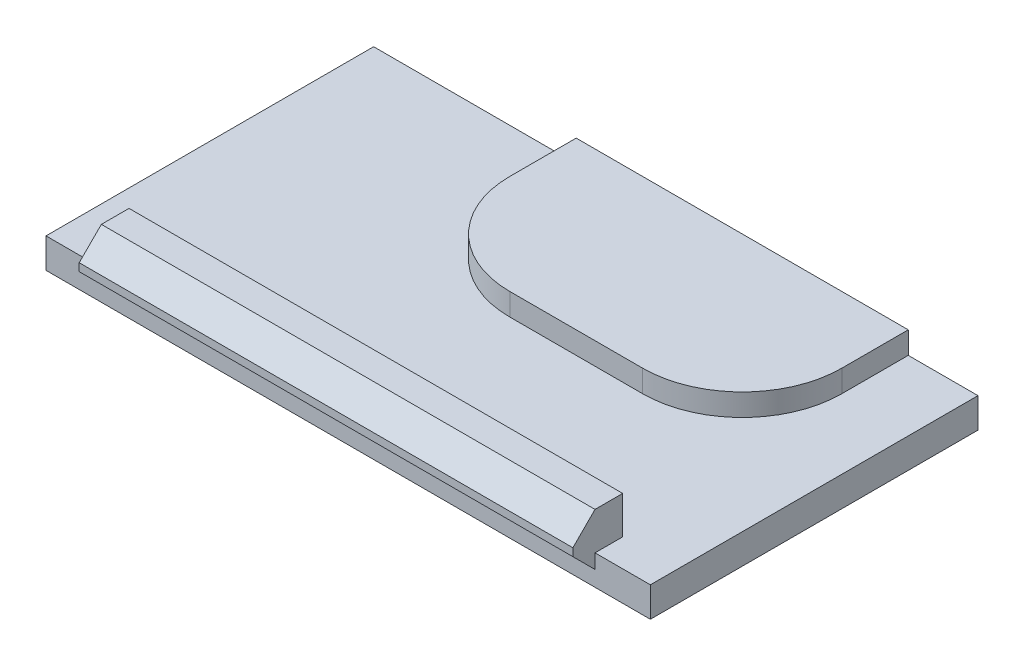
SolidWorks part; units mm, degrees
ref_plane "Front Plane" through (0, 0, 0) normal (0, 0, 1) x (1, 0, 0)
ref_plane "Top Plane" through (0, 0, 0) normal (0, 1, 0) x (1, 0, 0)
ref_plane "Right Plane" through (0, 0, 0) normal (1, 0, 0) x (0, 0, -1)
sketch "Sketch1" plane through (0, 0, 0) normal (0, 1, 0) x (1, 0, 0)
  line L1 (0, 0) -> (69.342, 0)
  line L2 (0, 0) -> (0, 37.592)
  line L3 (0, 37.592) -> (69.342, 37.592)
  line L4 (69.342, 0) -> (69.342, 37.592)
  dimension "D1" = 69.342
  dimension "D2" = 37.592
extrude "Boss-Extrude1" add sketch "Sketch1" along normal blind 3.429
sketch "Sketch3" plane through (0, 0, 0) normal (0, -1, 0) x (1, 0, 0)
  line L0 (34.671, 0) -> (34.671, -22.352) construction
  line L1 (0, 0) -> (69.342, 0) construction
  line L2 (69.342, -37.592) -> (0, -37.592) construction
  line L10 (34.671, -22.352) -> (49.911, -22.352)
  line L11 (57.531, -29.972) -> (57.531, -37.592)
  line L14 (27.051, -29.972) -> (27.051, -37.592)
  line L16 (57.531, -37.592) -> (27.051, -37.592)
  arc A2 (34.671, -22.352) -> (27.051, -29.972) centre (34.671, -29.972) ccw
  arc A3 (57.531, -29.972) -> (49.911, -22.352) centre (49.911, -29.972) ccw
  dimension "D1" = 15.24
  dimension "D3" = 7.62
  dimension "D2" = 15.24
  dimension "D4" = 7.62
  dimension "D5" = 15.24
extrude "Cut-Extrude1" cut sketch "Sketch3" against normal up to surface (3.429 mm away) up to face at (34.671, 3.429, -18.796)
sketch "Sketch5" plane through (0, 0, 0) normal (0, 0, 1) x (1, 0, 0)
  line L0 (0, 3.429) -> (0, 0) construction
  line L1 (6.35, 1.5875) -> (62.992, 1.5875)
  line L2 (6.35, 1.5875) -> (6.35, 7.9375)
  line L3 (6.35, 7.9375) -> (62.992, 7.9375)
  line L4 (62.992, 1.5875) -> (62.992, 7.9375)
  line L5 (69.342, 3.429) -> (69.342, 0) construction
  line L6 (0, 0) -> (69.342, 0) construction
  dimension "D1" = 6.35
  dimension "D2" = 6.35
  dimension "D3" = 1.5875
  dimension "D4" = 6.35
extrude "Boss-Extrude3" add sketch "Sketch5" along normal blind 2.54
chamfer "Chamfer1" distance 2.7305 angle 45 2 edges at (34.671, 1.5875, 2.54) (34.671, 7.9375, 2.54)
sketch "Sketch6" plane through (0, 0, 0) normal (0, 0, -1) x (-1, 0, 0)
  line L5 (-62.992, 7.747) -> (-6.35, 7.747)
  line L6 (-62.992, 7.747) -> (-62.992, 3.429)
  line L7 (-62.992, 3.429) -> (-6.35, 3.429)
  line L8 (-6.35, 7.747) -> (-6.35, 3.429)
extrude "Boss-Extrude4" add sketch "Sketch6" along normal blind 3.175
sketch "Sketch7" plane through (0, 0, 0) normal (0, -1, 0) x (1, 0, 0)
  line L0 (0, -9.017) -> (69.342, -9.017) construction
  line L1 (0, -37.592) -> (0, 0) construction
  line L2 (69.342, 0) -> (69.342, -37.592) construction
  line L4 (49.911, -22.352) -> (34.671, -22.352) construction
  text T0 "<b>BATTERY</b>" font "Arial Rounded MT Bold" height 6.35
  dimension "D1" = 13.335
extrude "Cut-Extrude2" cut sketch "Sketch7" against normal blind 0.4
sketch "Sketch8" plane through (0, 3.429, 0) normal (0, 1, 0) x (1, 0, 0)
  line L0 (61.341, 37.592) -> (61.341, 18.542)
  line L1 (69.342, 37.592) -> (57.531, 37.592) construction
  line L2 (34.671, 18.542) -> (61.341, 18.542)
  line L3 (23.241, 29.972) -> (23.241, 37.592)
  line L4 (27.051, 37.592) -> (0, 37.592) construction
  line L5 (27.051, 29.972) -> (27.051, 37.592) construction
  line L6 (57.531, 37.592) -> (57.531, 29.972) construction
  line L11 (49.911, 22.352) -> (34.671, 22.352) construction
  line L12 (61.341, 37.592) -> (23.241, 37.592)
  arc A0 (23.241, 29.972) -> (34.671, 18.542) centre (34.671, 29.972) ccw
  arc A1 (27.051, 29.972) -> (34.671, 22.352) centre (34.671, 29.972) ccw construction
  arc A2 (49.911, 18.542) -> (61.341, 29.972) centre (49.911, 29.972) ccw
  arc A3 (49.911, 22.352) -> (57.531, 29.972) centre (49.911, 29.972) ccw construction
  line M8 (69.342, 37.592) -> (57.531, 37.592)
  line M9 (57.531, 37.592) -> (57.531, 29.972)
  arc M10 (57.531, 29.972) -> (49.911, 22.352) centre (49.911, 29.972) cw
  line M11 (49.911, 22.352) -> (34.671, 22.352)
  arc M12 (34.671, 22.352) -> (27.051, 29.972) centre (34.671, 29.972) cw
  line M13 (27.051, 29.972) -> (27.051, 37.592)
  line M14 (27.051, 37.592) -> (0, 37.592)
  dimension "D1" = 3.81
  dimension "D2" = 3.81
  dimension "D3" = 3.81
extrude "Boss-Extrude5" add sketch "Sketch8" along normal blind 2.54 contours L2 A2 L0 L3 A0 M8 M9 M10 M11 M12 M13 M14 | L12 M9 M13 M12 M11 M10 region at (60.915, 3.429, -33.782) region at (42.291, 3.429, -30.3075)
sketch "Sketch9" plane through (0, 3.429, 0) normal (0, -1, 0) x (1, 0, 0)
  line L0 (27.051, -37.592) -> (57.531, -37.592)
  line L1 (57.531, -37.592) -> (57.531, -29.972)
  line L2 (49.911, -22.352) -> (34.671, -22.352)
  line L3 (27.051, -37.592) -> (27.051, -29.972)
  arc A0 (27.051, -29.972) -> (34.671, -22.352) centre (34.671, -29.972) cw
  arc A1 (57.531, -29.972) -> (49.911, -22.352) centre (49.911, -29.972) ccw
  arc A2 (34.671, -22.352) -> (27.051, -29.972) centre (34.671, -29.972) ccw construction
  arc A3 (57.531, -29.972) -> (49.911, -22.352) centre (49.911, -29.972) ccw construction
extrude "Cut-Extrude3" cut sketch "Sketch9" against normal blind 0.635
sketch "Sketch10" plane through (0, 0.4, 0) normal (0, -1, 0) x (1, 0, 0)
  line L0 (52.4609, -14.097) -> (53.3241, -14.097) construction
  line L1 (53.3241, -14.097) -> (53.3241, -12.7476) construction
  line L2 (53.3241, -12.7476) -> (52.3332, -12.7476) construction
  line L3 (51.9599, -15.2082) -> (53.9281, -15.2082) construction
  line L4 (54.7529, -14.3798) -> (54.7529, -9.8455) construction
  line L5 (53.9281, -9.017) -> (52.0727, -9.017) construction
  line L6 (52.1769, -11.7157) -> (53.3241, -11.7157) construction
  line L7 (53.3241, -11.7157) -> (53.3241, -10.1282) construction
  line L8 (53.3241, -10.1282) -> (52.1347, -10.1282) construction
  line L9 (43.2807, -10.2436) -> (44.8657, -14.1565) construction
  line L10 (47.1664, -14.097) -> (48.6981, -10.2089) construction
  line L11 (47.3995, -9.7401) -> (47.1329, -10.4457) construction
  line L12 (47.1329, -10.4457) -> (44.8806, -10.4457) construction
  line L13 (44.8806, -10.4457) -> (44.6127, -9.7549) construction
  line L14 (45.2304, -11.557) -> (46.0167, -13.8589) construction
  line L15 (46.0167, -13.8589) -> (46.7819, -11.557) construction
  line L16 (46.7819, -11.557) -> (45.2304, -11.557) construction
  line L17 (38.1809, -15.2082) -> (42.0343, -15.2082) construction
  line L18 (42.0343, -14.0176) -> (40.7829, -14.0176) construction
  line L19 (40.7829, -14.0176) -> (40.7829, -9.7549) construction
  line L20 (39.3541, -9.7549) -> (39.3541, -14.0176) construction
  line L21 (39.3541, -14.0176) -> (38.1809, -14.0176) construction
  line L22 (32.704, -15.2082) -> (36.5574, -15.2082) construction
  line L23 (36.5574, -14.0176) -> (35.306, -14.0176) construction
  line L24 (35.306, -14.0176) -> (35.306, -9.7549) construction
  line L25 (33.8772, -9.7549) -> (33.8772, -14.0176) construction
  line L26 (33.8772, -14.0176) -> (32.704, -14.0176) construction
  line L27 (27.2395, -15.2082) -> (30.4492, -15.2082) construction
  line L28 (31.2579, -14.3798) -> (31.2579, -9.8455) construction
  line L29 (30.4492, -9.017) -> (27.1453, -9.017) construction
  line L30 (27.1453, -10.1282) -> (29.8291, -10.1282) construction
  line L31 (29.8291, -10.1282) -> (29.8291, -11.7157) construction
  line L32 (29.8291, -11.7157) -> (27.4578, -11.7157) construction
  line L33 (27.4578, -12.827) -> (29.8291, -12.827) construction
  line L34 (29.8291, -12.827) -> (29.8291, -14.097) construction
  line L35 (29.8291, -14.097) -> (27.2395, -14.097) construction
  line L36 (16.4147, -9.7562) -> (16.4147, -11.6513) construction
  line L37 (16.4147, -11.6513) -> (14.9339, -13.9097) construction
  line L38 (16.091, -14.541) -> (17.113, -12.7476) construction
  line L39 (17.113, -12.7476) -> (18.1226, -14.541) construction
  line L40 (19.3033, -13.8787) -> (17.8435, -11.6302) construction
  line L41 (17.8435, -11.6302) -> (17.8435, -9.7562) construction
  line L42 (23.0252, -14.097) -> (24.0347, -14.097) construction
  line L43 (24.0347, -14.097) -> (24.0347, -12.5889) construction
  line L44 (24.0347, -12.5889) -> (23.0599, -12.5889) construction
  line L45 (22.3356, -10.5301) -> (21.8532, -9.7339) construction
  line L46 (22.6172, -15.2082) -> (24.6263, -15.2082) construction
  line L47 (25.4635, -14.3823) -> (25.4635, -9.7587) construction
  line L48 (24.0347, -9.7438) -> (24.0347, -11.557) construction
  line L49 (24.0347, -11.557) -> (23.7507, -11.557) construction
  line L50 (52.4609, -14.097) -> (53.3241, -14.097)
  line L51 (53.3241, -14.097) -> (53.3241, -12.7476)
  line L52 (53.3241, -12.7476) -> (52.3332, -12.7476)
  line L53 (51.9599, -15.2082) -> (53.9281, -15.2082)
  line L54 (54.7529, -14.3798) -> (54.7529, -9.8455)
  line L55 (53.9281, -9.017) -> (52.0727, -9.017)
  line L56 (52.1769, -11.7157) -> (53.3241, -11.7157)
  line L57 (53.3241, -11.7157) -> (53.3241, -10.1282)
  line L58 (53.3241, -10.1282) -> (52.1347, -10.1282)
  line L59 (43.2807, -10.2436) -> (44.8657, -14.1565)
  line L60 (47.1664, -14.097) -> (48.6981, -10.2089)
  line L61 (47.3995, -9.7401) -> (47.1329, -10.4457)
  line L62 (47.1329, -10.4457) -> (44.8806, -10.4457)
  line L63 (44.8806, -10.4457) -> (44.6127, -9.7549)
  line L64 (45.2304, -11.557) -> (46.0167, -13.8589)
  line L65 (46.0167, -13.8589) -> (46.7819, -11.557)
  line L66 (46.7819, -11.557) -> (45.2304, -11.557)
  line L67 (38.1809, -15.2082) -> (42.0343, -15.2082)
  line L68 (42.0343, -14.0176) -> (40.7829, -14.0176)
  line L69 (40.7829, -14.0176) -> (40.7829, -9.7549)
  line L70 (39.3541, -9.7549) -> (39.3541, -14.0176)
  line L71 (39.3541, -14.0176) -> (38.1809, -14.0176)
  line L72 (32.704, -15.2082) -> (36.5574, -15.2082)
  line L73 (36.5574, -14.0176) -> (35.306, -14.0176)
  line L74 (35.306, -14.0176) -> (35.306, -9.7549)
  line L75 (33.8772, -9.7549) -> (33.8772, -14.0176)
  line L76 (33.8772, -14.0176) -> (32.704, -14.0176)
  line L77 (27.2395, -15.2082) -> (30.4492, -15.2082)
  line L78 (31.2579, -14.3798) -> (31.2579, -9.8455)
  line L79 (30.4492, -9.017) -> (27.1453, -9.017)
  line L80 (27.1453, -10.1282) -> (29.8291, -10.1282)
  line L81 (29.8291, -10.1282) -> (29.8291, -11.7157)
  line L82 (29.8291, -11.7157) -> (27.4578, -11.7157)
  line L83 (27.4578, -12.827) -> (29.8291, -12.827)
  line L84 (29.8291, -12.827) -> (29.8291, -14.097)
  line L85 (29.8291, -14.097) -> (27.2395, -14.097)
  line L86 (16.4147, -9.7562) -> (16.4147, -11.6513)
  line L87 (16.4147, -11.6513) -> (14.9339, -13.9097)
  line L88 (16.091, -14.541) -> (17.113, -12.7476)
  line L89 (17.113, -12.7476) -> (18.1226, -14.541)
  line L90 (19.3033, -13.8787) -> (17.8435, -11.6302)
  line L91 (17.8435, -11.6302) -> (17.8435, -9.7562)
  line L92 (23.0252, -14.097) -> (24.0347, -14.097)
  line L93 (24.0347, -14.097) -> (24.0347, -12.5889)
  line L94 (24.0347, -12.5889) -> (23.0599, -12.5889)
  line L95 (22.3356, -10.5301) -> (21.8532, -9.7339)
  line L96 (22.6172, -15.2082) -> (24.6263, -15.2082)
  line L97 (25.4635, -14.3823) -> (25.4635, -9.7587)
  line L98 (24.0347, -9.7438) -> (24.0347, -11.557)
  line L99 (24.0347, -11.557) -> (23.7507, -11.557)
  spline S0 degree 3 poles (-1943.9789, -151.7713) (70.8015, -5.7564) (50.7068, -10.4378) (51.201, -13.6216) (51.2243, -13.6995) (51.2587, -13.7692) (51.302, -13.8313) (51.3548, -13.8859) (51.418, -13.9304) (51.4902, -13.9682) (51.5729, -13.9988) (51.6666, -14.0239) (51.7709, -14.0487) (51.8874, -14.064) (52.0145, -14.0802) (52.1532, -14.089) (59.2271, -14.3943) (66.7012, 1.2782) (17.369, -2013.7103) knots -5.753764 -5.753764 -5.753764 -5.753764 0.057159 0.110334 0.159685 0.206314 0.252763 0.298508 0.345397 0.394418 0.448129 0.507403 0.572945 0.645272 0.723434 0.808888 0.901053 13.757311 13.757311 13.757311 13.757311 only from (51.1847, -13.4446) to (52.4609, -14.097) construction
  spline S1 degree 3 poles (27.8312, 1987.0169) (67.0369, -32.6557) (59.2752, -12.2766) (51.9392, -12.7629) (51.7799, -12.7871) (51.6453, -12.8198) (51.5313, -12.8664) (51.4342, -12.9309) (49.1681, -15.1401) (68.6101, -34.1998) (-1532.3859, 1208.2321) knots -18.431036 -18.431036 -18.431036 -18.431036 0.185293 0.345415 0.484392 0.599814 0.701445 0.799771 0.898391 8.784418 8.784418 8.784418 8.784418 only from (52.3332, -12.7476) to (51.2864, -13.111) construction
  spline S2 degree 3 poles (-1741.3145, 873.7381) (75.0574, -19.1103) (52.1018, -10.769) (51.2096, -13.2703) (50.5576, -15.8045) (74.5308, -21.6465) (-1931.6532, 247.6794) knots -21.680999 -21.680999 -21.680999 -21.680999 0.254449 0.501939 0.746908 22.345073 22.345073 22.345073 22.345073 only from (51.2864, -13.111) to (51.1847, -13.4446) construction
  spline S3 degree 3 poles (75.2742, 1990.7471) (73.5276, -23.7791) (62.5688, -8.6736) (51.6082, -9.0272) (51.3953, -9.0456) (51.1961, -9.0671) (51.0106, -9.0958) (50.8392, -9.1364) (46.0755, -10.4981) (48.895, -33.3987) (-622.2815, 1874.0357) knots -20.541444 -20.541444 -20.541444 -20.541444 0.154275 0.299144 0.435657 0.563025 0.682412 0.794474 0.900098 10.150863 10.150863 10.150863 10.150863 only from (52.0727, -9.017) to (50.5311, -9.2415) construction
  spline S4 degree 3 poles (-855.1089, 1773.8437) (67.7349, -22.8697) (54.3326, -7.0026) (50.298, -9.365) (50.1923, -9.437) (50.0934, -9.5151) (50.0036, -9.6016) (49.9178, -9.6914) (49.8432, -9.7905) (49.7502, -9.9266) (49.6557, -10.1086) (49.5748, -10.3396) (48.3854, -15.8394) (80.0906, -24.7646) (-1940.7703, 185.1892) knots -6.819457 -6.819457 -6.819457 -6.819457 0.067226 0.13264 0.196559 0.259324 0.321719 0.383688 0.445686 0.50788 0.631239 0.752454 0.874886 9.044969 9.044969 9.044969 9.044969 only from (50.5311, -9.2415) to (49.5141, -10.829) construction
  spline S5 degree 3 poles (-1948.8407, -90.6734) (67.7035, 0.043) (49.0618, -5.9605) (49.5296, -11.0996) (49.5514, -11.2271) (49.5845, -11.3478) (49.6237, -11.4632) (49.6736, -11.5715) (49.7308, -11.6753) (49.7991, -11.771) (49.8756, -11.8612) (49.9601, -11.9461) (50.0543, -12.0242) (50.1584, -12.0947) (50.27, -12.1608) (50.3908, -12.2201) (55.0009, -14.1417) (66.6884, 3.6787) (-614.5547, -1898.3784) knots -7.400285 -7.400285 -7.400285 -7.400285 0.068275 0.133744 0.197443 0.258623 0.317963 0.376852 0.434131 0.492274 0.549763 0.608348 0.668487 0.729827 0.793456 0.859389 0.927948 8.146244 8.146244 8.146244 8.146244 only from (49.5141, -10.829) to (50.6576, -12.3185) construction
  spline S6 degree 3 poles (-897.2535, 1748.6719) (74.1327, -33.6168) (54.7821, -9.4709) (50.2766, -12.5349) (50.1241, -12.6713) (50.001, -12.8279) (49.904, -13.0009) (49.836, -13.1921) (48.7938, -18.3765) (78.6773, -26.4785) (-1942.2599, 163.412) knots -9.367601 -9.367601 -9.367601 -9.367601 0.137227 0.264577 0.386073 0.503501 0.620912 0.74101 0.866757 10.080854 10.080854 10.080854 10.080854 only from (50.6576, -12.3185) to (49.787, -13.6183) construction
  spline S7 degree 3 poles (-1946.3622, -137.1057) (71.1077, -4.2782) (49.2535, -9.8137) (49.8066, -13.8713) (49.8324, -13.995) (49.8694, -14.1164) (49.9183, -14.2344) (49.9764, -14.3486) (50.0452, -14.4586) (50.1248, -14.5641) (50.2149, -14.6645) (50.3173, -14.7582) (53.9436, -17.663) (70.7025, -1.8777) (-1091.451, -1656.7262) knots -7.489608 -7.489608 -7.489608 -7.489608 0.080578 0.160182 0.239294 0.319412 0.399689 0.480449 0.561571 0.644746 0.729985 0.816279 0.906989 9.502461 9.502461 9.502461 9.502461 only from (49.787, -13.6183) to (50.5522, -14.9267) construction
  spline S8 degree 3 poles (-857.5216, -1796.8604) (53.9426, 10.6843) (46.7348, -13.3983) (50.8327, -15.0633) (50.9896, -15.1136) (51.1592, -15.1504) (51.3414, -15.1749) (51.5357, -15.1955) (59.704, -15.6145) (68.1738, 3.1103) (37.5551, -2015.083) knots -8.780462 -8.780462 -8.780462 -8.780462 0.105008 0.213242 0.326042 0.444876 0.570736 0.705393 0.848096 17.443439 17.443439 17.443439 17.443439 only from (50.5522, -14.9267) to (51.9599, -15.2082) construction
  spline S9 degree 3 poles (155.5885, -2012.5118) (45.847, 4.303) (50.5415, -15.6005) (54.1253, -15.1968) (54.2148, -15.183) (54.2963, -15.1602) (54.3715, -15.1329) (54.4404, -15.1004) (54.5, -15.0581) (54.5546, -15.0121) (54.6021, -14.9585) (54.6417, -14.8964) (54.6763, -14.8283) (54.7057, -14.753) (54.7253, -14.6697) (54.7426, -14.5797) (55.1003, -9.9382) (39.728, -5.0777) (2054.5605, -32.425) knots -7.783832 -7.783832 -7.783832 -7.783832 0.076201 0.148167 0.214256 0.277045 0.3357 0.391934 0.445397 0.497463 0.550131 0.603846 0.660491 0.719468 0.78291 0.850062 0.922854 11.100782 11.100782 11.100782 11.100782 only from (53.9281, -15.2082) to (54.7529, -14.3798) construction
  spline S10 degree 3 poles (2048.4091, 148.4974) (26.3681, -21.4738) (55.6697, -14.1967) (54.7114, -9.4815) (54.6507, -9.3355) (54.5787, -9.2342) (54.5077, -9.1704) (54.4474, -9.1289) (54.3791, -9.0948) (54.3036, -9.0657) (54.2204, -9.044) (54.1296, -9.0276) (49.5866, -8.6633) (44.5929, -24.571) (99.7067, 1990.3965) knots -10.227206 -10.227206 -10.227206 -10.227206 0.147169 0.275723 0.390478 0.496241 0.548237 0.60171 0.658367 0.717356 0.781044 0.849113 0.92192 10.888797 10.888797 10.888797 10.888797 only from (54.7529, -9.8455) to (53.9281, -9.017) construction
  spline S11 degree 3 poles (13.7612, 1989.4029) (64.6234, -25.7659) (58.0308, -9.7722) (51.8582, -10.139) (51.7322, -10.1548) (51.6157, -10.1779) (51.5078, -10.2039) (51.4095, -10.2388) (51.3207, -10.28) (51.2403, -10.3265) (51.171, -10.3821) (51.1092, -10.4413) (51.0577, -10.5084) (51.0156, -10.5814) (50.9829, -10.6611) (50.9595, -10.7464) (50.4611, -14.081) (70.7012, -18.8697) (-1944.5328, 121.9921) knots -11.105427 -11.105427 -11.105427 -11.105427 0.088131 0.171088 0.249183 0.321128 0.389284 0.452942 0.512406 0.568937 0.623027 0.675123 0.726015 0.777734 0.829497 0.883853 0.939923 7.006783 7.006783 7.006783 7.006783 only from (52.1347, -10.1282) to (50.9429, -10.9344) construction
  spline S12 degree 3 poles (-1943.819, -155.0347) (70.5687, -2.8555) (50.4617, -7.7698) (50.9595, -11.1232) (50.9823, -11.209) (51.0173, -11.2871) (51.0583, -11.3596) (51.112, -11.4233) (51.1733, -11.4811) (51.2444, -11.5323) (51.3264, -11.5751) (51.4172, -11.6145) (51.5196, -11.6442) (51.6313, -11.6703) (51.753, -11.6914) (51.8852, -11.706) (57.7181, -12.0627) (64.0114, 6.0503) (14.6689, -2011.2893) knots -5.940677 -5.940677 -5.940677 -5.940677 0.059054 0.114906 0.168336 0.218822 0.269014 0.318338 0.368513 0.420932 0.476046 0.535256 0.599256 0.668251 0.742506 0.822147 0.908161 11.290304 11.290304 11.290304 11.290304 only from (50.9429, -10.9344) to (52.1769, -11.7157) construction
  spline S13 degree 3 poles (1889.0208, 763.3381) (40.1427, -30.9104) (48.1046, -17.6856) (44.4871, -9.4615) (44.4351, -9.3503) (44.3937, -9.275) (44.3551, -9.2083) (44.3005, -9.1364) (44.2261, -9.0584) (44.1351, -9.0012) (44.0538, -8.9683) (43.987, -8.9493) (40.9062, -8.5559) (36.9601, -26.2638) (132.8358, 1988.9717) knots -21.798818 -21.798818 -21.798818 -21.798818 0.13391 0.28778 0.36578 0.436508 0.499646 0.555736 0.658858 0.763824 0.817797 0.874951 0.93466 8.455922 8.455922 8.455922 8.455922 only from (44.6127, -9.7549) to (43.8363, -8.9376) construction
  spline S14 degree 3 poles (-228.4966, 1972.4089) (55.1556, -38.6805) (47.0998, -7.9486) (43.5335, -8.9855) (43.4013, -9.049) (43.2921, -9.1421) (43.2024, -9.2447) (43.1351, -9.3513) (42.1349, -11.9942) (69.606, -20.0808) (-1922.2546, 360.977) knots -9.78094 -9.78094 -9.78094 -9.78094 0.148047 0.284632 0.417677 0.550997 0.678335 0.793924 0.898525 8.401692 8.401692 8.401692 8.401692 only from (43.8363, -8.9376) to (43.0848, -9.5726) construction
  spline S15 degree 3 poles (-1947.6905, -200.7556) (60.8584, -3.7542) (42.7029, -7.6304) (43.0978, -9.6927) (43.1114, -9.7644) (43.1353, -9.8437) (43.1621, -9.932) (43.1957, -10.0284) (45.7013, -16.5624) (59.5149, -18.5707) (-1807.8039, -767.3062) knots -8.673153 -8.673153 -8.673153 -8.673153 0.077776 0.167189 0.271774 0.38917 0.520423 0.666174 0.8249 30.409144 30.409144 30.409144 30.409144 only from (43.0848, -9.5726) to (43.2807, -10.2436) construction
  spline S16 degree 3 poles (-1828.3451, -714.6246) (52.5283, 2.3608) (42.5469, -8.3707) (44.9491, -14.373) (44.9858, -14.4685) (45.0322, -14.5846) (45.0995, -14.7251) (45.1824, -14.8609) (45.2635, -14.9678) (45.3415, -15.0406) (45.4277, -15.1109) (45.5275, -15.1727) (45.6386, -15.2259) (45.764, -15.2609) (49.928, -15.96) (56.2344, 8.8146) (-112.7178, -2008.8815) knots -10.715981 -10.715981 -10.715981 -10.715981 0.0693 0.13224 0.189872 0.241804 0.34318 0.452148 0.509767 0.568952 0.63147 0.697263 0.766528 0.838472 0.916207 7.870541 7.870541 7.870541 7.870541 only from (44.8657, -14.1565) to (46.0464, -15.2876) construction
  spline S17 degree 3 poles (227.1236, -2007.0387) (36.7065, 8.9883) (42.7124, -15.9363) (46.2934, -15.2626) (46.4048, -15.2318) (46.504, -15.1833) (46.5936, -15.1263) (46.6731, -15.0614) (46.7442, -14.9904) (46.8033, -14.909) (46.8586, -14.8211) (46.9102, -14.7242) (46.96, -14.6182) (47.0064, -14.5054) (47.0514, -14.3929) (47.0918, -14.2857) (52.4137, -0.838) (53.5781, 14.1515) (1931.0551, -685.1146) knots -5.939023 -5.939023 -5.939023 -5.939023 0.072802 0.141659 0.205819 0.267746 0.327487 0.385145 0.441017 0.496954 0.554765 0.616707 0.682392 0.752905 0.822889 0.887297 0.946635 25.283211 25.283211 25.283211 25.283211 only from (46.0464, -15.2876) to (47.1664, -14.097) construction
  spline S18 degree 3 poles (-1841.746, 642.3404) (48.3358, -31.8255) (44.9098, -19.61) (48.7791, -10.0061) (48.8095, -9.9193) (48.8433, -9.821) (49.7323, -6.2555) (23.1172, 0.7627) (2034.2221, -250.0231) knots -45.606813 -45.606813 -45.606813 -45.606813 0.174246 0.330388 0.467148 0.583513 0.793268 16.72326 16.72326 16.72326 16.72326 only from (48.6981, -10.2089) to (48.8791, -9.5639) construction
  spline S19 degree 3 poles (2023.1136, 310.0857) (21.4366, -19.8859) (49.8104, -12.1867) (48.8327, -9.3279) (48.7692, -9.2205) (48.6826, -9.1247) (48.5817, -9.0419) (48.4686, -8.9811) (45.2963, -8.0443) (38.0847, -35.465) (323.8122, 1971.9326) knots -8.560975 -8.560975 -8.560975 -8.560975 0.12044 0.238784 0.360584 0.49095 0.622696 0.748676 0.872186 10.41275 10.41275 10.41275 10.41275 only from (48.8791, -9.5639) to (48.2193, -8.9376) construction
  spline S20 degree 3 poles (-137.3088, 1982.3533) (59.0281, -36.9065) (52.0112, -8.0415) (47.9095, -8.9774) (47.79, -9.0373) (47.6982, -9.1273) (47.6257, -9.2436) (47.55, -9.3822) (44.5322, -16.0458) (60.7089, -30.3103) (-1817.9892, 711.4557) knots -9.635638 -9.635638 -9.635638 -9.635638 0.13688 0.253973 0.356631 0.45249 0.557304 0.683472 0.830438 18.044171 18.044171 18.044171 18.044171 only from (48.2193, -8.9376) to (47.3995, -9.7401) construction
  spline S21 degree 3 poles (-103.7297, 1980.8587) (49.2595, -40.8063) (42.4639, -13.1778) (37.8417, -14.0543) (37.704, -14.1107) (37.5922, -14.1883) (37.5058, -14.2809) (37.4434, -14.383) (36.4837, -17.187) (64.4966, -24.7389) (-1937.1132, 303.1288) knots -12.301471 -12.301471 -12.301471 -12.301471 0.167084 0.315373 0.447217 0.569444 0.683458 0.790136 0.893477 8.6641 8.6641 8.6641 8.6641 only from (38.1809, -14.0176) to (37.3983, -14.6105) construction
  spline S22 degree 3 poles (-1935.2386, -344.0123) (64.6509, -4.324) (36.4781, -12.0566) (37.4438, -14.8379) (37.5043, -14.9408) (37.5884, -15.0353) (37.6992, -15.1148) (37.8379, -15.1696) (42.3105, -16.0888) (49.6046, 12.9995) (-139.1894, -2007.2374) knots -7.584969 -7.584969 -7.584969 -7.584969 0.106091 0.209012 0.315647 0.428514 0.549976 0.682321 0.830233 12.882208 12.882208 12.882208 12.882208 only from (37.3983, -14.6105) to (38.1809, -15.2082) construction
  spline S23 degree 3 poles (208.7338, -2008.2225) (31.8891, 11.1843) (38.3406, -16.0087) (42.3259, -15.1739) (42.4471, -15.1225) (42.5496, -15.0528) (42.6311, -14.9642) (42.6884, -14.8589) (43.6292, -11.7695) (14.6333, -4.4309) (2023.7371, -289.1128) knots -11.280839 -11.280839 -11.280839 -11.280839 0.150861 0.286561 0.411296 0.528962 0.642296 0.755686 0.872884 9.882478 9.882478 9.882478 9.882478 only from (42.0343, -15.2082) to (42.73, -14.6105) construction
  spline S24 degree 3 poles (2029.5085, 214.3281) (16.4212, -24.0843) (43.5725, -17.5636) (42.6915, -14.3691) (42.6336, -14.2666) (42.5558, -14.1771) (42.4562, -14.1035) (42.3332, -14.0532) (38.3606, -13.1889) (31.505, -41.2967) (231.3926, 1976.8915) knots -9.156947 -9.156947 -9.156947 -9.156947 0.122738 0.237333 0.348401 0.461386 0.578861 0.703987 0.84388 12.29944 12.29944 12.29944 12.29944 only from (42.73, -14.6105) to (42.0343, -14.0176) construction
  spline S25 degree 3 poles (2030.9468, 188.1811) (11.5986, -21.3997) (41.7054, -13.7815) (40.7415, -9.4045) (40.6846, -9.2599) (40.5993, -9.1434) (40.4978, -9.0505) (40.3792, -8.9851) (37.1229, -7.962) (29.2943, -38.0807) (323.7978, 1970.7629) knots -10.715216 -10.715216 -10.715216 -10.715216 0.158301 0.298899 0.425305 0.543693 0.656317 0.766369 0.879744 9.094274 9.094274 9.094274 9.094274 only from (40.7829, -9.7549) to (40.1045, -8.9376) construction
  spline S26 degree 3 poles (-205.1113, 1975.9259) (51.3929, -38.2463) (43.589, -7.9388) (39.7895, -8.9862) (39.6568, -9.0543) (39.5469, -9.1517) (39.4588, -9.2721) (39.3979, -9.4156) (38.4158, -13.672) (67.8848, -21.2059) (-1950.0947, 195.1047) knots -8.949186 -8.949186 -8.949186 -8.949186 0.133584 0.256326 0.371023 0.486346 0.603522 0.72409 0.855671 10.960583 10.960583 10.960583 10.960583 only from (40.1045, -8.9376) to (39.3541, -9.7549) construction
  spline S27 degree 3 poles (-109.2066, 1980.8587) (43.7826, -40.8063) (36.9871, -13.1778) (32.3648, -14.0543) (32.2272, -14.1107) (32.1153, -14.1883) (32.0289, -14.2809) (31.9665, -14.383) (31.0068, -17.187) (59.0197, -24.7389) (-1942.59, 303.1288) knots -12.301471 -12.301471 -12.301471 -12.301471 0.167084 0.315373 0.447217 0.569444 0.683458 0.790136 0.893477 8.6641 8.6641 8.6641 8.6641 only from (32.704, -14.0176) to (31.9214, -14.6105) construction
  spline S28 degree 3 poles (-1940.7155, -344.0123) (59.174, -4.324) (31.0013, -12.0566) (31.9669, -14.8379) (32.0274, -14.9408) (32.1115, -15.0353) (32.2223, -15.1148) (32.361, -15.1696) (36.8336, -16.0888) (44.1278, 12.9995) (-144.6663, -2007.2374) knots -7.584969 -7.584969 -7.584969 -7.584969 0.106091 0.209012 0.315647 0.428514 0.549976 0.682321 0.830233 12.882208 12.882208 12.882208 12.882208 only from (31.9214, -14.6105) to (32.704, -15.2082) construction
  spline S29 degree 3 poles (203.2569, -2008.2225) (26.4122, 11.1843) (32.8637, -16.0087) (36.849, -15.1739) (36.9702, -15.1225) (37.0727, -15.0528) (37.1542, -14.9642) (37.2115, -14.8589) (38.1524, -11.7695) (9.1564, -4.4309) (2018.2602, -289.1128) knots -11.280839 -11.280839 -11.280839 -11.280839 0.150861 0.286561 0.411296 0.528962 0.642296 0.755686 0.872884 9.882478 9.882478 9.882478 9.882478 only from (36.5574, -15.2082) to (37.2532, -14.6105) construction
  spline S30 degree 3 poles (2024.0316, 214.3281) (10.9443, -24.0843) (38.0956, -17.5636) (37.2146, -14.3691) (37.1568, -14.2666) (37.0789, -14.1771) (36.9793, -14.1035) (36.8563, -14.0532) (32.8838, -13.1889) (26.0281, -41.2967) (225.9157, 1976.8915) knots -9.156947 -9.156947 -9.156947 -9.156947 0.122738 0.237333 0.348401 0.461386 0.578861 0.703987 0.84388 12.29944 12.29944 12.29944 12.29944 only from (37.2532, -14.6105) to (36.5574, -14.0176) construction
  spline S31 degree 3 poles (2025.4699, 188.1811) (6.1217, -21.3997) (36.2285, -13.7815) (35.2646, -9.4045) (35.2077, -9.2599) (35.1224, -9.1434) (35.021, -9.0505) (34.9023, -8.9851) (31.6461, -7.962) (23.8174, -38.0807) (318.321, 1970.7629) knots -10.715216 -10.715216 -10.715216 -10.715216 0.158301 0.298899 0.425305 0.543693 0.656317 0.766369 0.879744 9.094274 9.094274 9.094274 9.094274 only from (35.306, -9.7549) to (34.6276, -8.9376) construction
  spline S32 degree 3 poles (-210.5882, 1975.9259) (45.916, -38.2463) (38.1122, -7.9388) (34.3126, -8.9862) (34.18, -9.0543) (34.07, -9.1517) (33.9819, -9.2721) (33.921, -9.4156) (32.939, -13.672) (62.4079, -21.2059) (-1955.5715, 195.1047) knots -8.949186 -8.949186 -8.949186 -8.949186 0.133584 0.256326 0.371023 0.486346 0.603522 0.72409 0.855671 10.960583 10.960583 10.960583 10.960583 only from (34.6276, -8.9376) to (33.8772, -9.7549) construction
  spline S33 degree 3 poles (-146.637, 1978.2694) (38.1798, -41.8857) (31.1912, -13.2618) (26.9171, -14.1325) (26.787, -14.1831) (26.6827, -14.2568) (26.6043, -14.3447) (26.5468, -14.4405) (25.6336, -17.1295) (53.3061, -24.4012) (-1949.1052, 296.4343) knots -12.109278 -12.109278 -12.109278 -12.109278 0.170179 0.31802 0.451116 0.571297 0.683982 0.789665 0.892964 8.80313 8.80313 8.80313 8.80313 only from (27.2395, -14.097) to (26.5053, -14.6551) construction
  spline S34 degree 3 poles (-1948.7905, -327.5382) (53.0681, -4.9988) (25.6376, -12.2165) (26.5468, -14.866) (26.6047, -14.9607) (26.6827, -15.0485) (26.7871, -15.1221) (26.9171, -15.1728) (31.1917, -16.0434) (38.1731, 12.5794) (-146.1359, -2007.6394) knots -7.728541 -7.728541 -7.728541 -7.728541 0.105133 0.207762 0.312895 0.426095 0.546824 0.680529 0.829044 13.16539 13.16539 13.16539 13.16539 only from (26.5053, -14.6551) to (27.2395, -15.2082) construction
  spline S35 degree 3 poles (182.4872, -2009.3938) (21.2565, 8.182) (26.9607, -15.7866) (30.6936, -15.1876) (30.8029, -15.1632) (30.9013, -15.1243) (30.9895, -15.0749) (31.0653, -15.0123) (31.127, -14.9361) (31.1756, -14.8476) (31.2124, -14.7471) (31.2394, -14.6352) (31.7883, -10.4369) (9.4276, -4.9588) (2028.5787, -116.9831) knots -8.198608 -8.198608 -8.198608 -8.198608 0.096564 0.185658 0.268697 0.347435 0.422238 0.494703 0.566577 0.640924 0.720196 0.806158 0.8988 10.199663 10.199663 10.199663 10.199663 only from (30.4492, -15.2082) to (31.2579, -14.3798) construction
  spline S36 degree 3 poles (2028.8832, 85.8576) (11.4786, -17.873) (31.6528, -13.2282) (31.2464, -9.6475) (31.2321, -9.5579) (31.2117, -9.475) (31.1835, -9.3999) (31.1522, -9.3306) (31.1118, -9.2701) (31.0667, -9.2153) (31.0145, -9.1682) (30.9546, -9.1278) (30.8879, -9.0936) (30.8141, -9.0644) (30.7326, -9.0444) (30.645, -9.0275) (26.2371, -8.6634) (21.4442, -24.6789) (68.1365, 1990.5144) knots -7.848323 -7.848323 -7.848323 -7.848323 0.077851 0.149578 0.217208 0.281253 0.340464 0.39683 0.451054 0.503014 0.555492 0.608175 0.664533 0.723206 0.785456 0.852333 0.923048 10.682382 10.682382 10.682382 10.682382 only from (31.2579, -9.8455) to (30.4492, -9.017) construction
  spline S37 degree 3 poles (-153.2094, 1982.81) (38.1033, -36.5685) (31.0712, -8.1849) (26.8254, -9.0525) (26.6945, -9.1032) (26.5902, -9.1785) (26.5091, -9.2652) (26.4506, -9.3601) (25.5154, -11.8992) (53.6017, -19.569) (-1943.9316, 333.4777) knots -12.094584 -12.094584 -12.094584 -12.094584 0.168627 0.317206 0.450967 0.573423 0.688294 0.794095 0.896019 8.456505 8.456505 8.456505 8.456505 only from (27.1453, -9.017) to (26.4073, -9.5689) construction
  spline S38 degree 3 poles (-1946.5503, -337.1793) (53.5266, 0.3364) (25.5188, -7.1657) (26.4504, -9.7829) (26.5098, -9.8793) (26.5915, -9.9671) (26.6963, -10.0417) (26.8274, -10.0911) (30.9209, -10.9904) (38.2078, 18.1867) (-175.0105, -1999.7819) knots -7.61385 -7.61385 -7.61385 -7.61385 0.105759 0.209355 0.317209 0.431416 0.554141 0.685573 0.83354 12.618076 12.618076 12.618076 12.618076 only from (26.4073, -9.5689) to (27.1453, -10.1282) construction
  spline S39 degree 3 poles (-122.2882, 1982.5915) (38.1884, -38.0651) (31.5436, -10.8921) (27.141, -11.7514) (27.0141, -11.8051) (26.9133, -11.8802) (26.8393, -11.9698) (26.7833, -12.0648) (25.9028, -14.7984) (52.2926, -21.648) (-1951.6619, 280.6796) knots -12.674779 -12.674779 -12.674779 -12.674779 0.169515 0.318688 0.450043 0.571741 0.684868 0.790079 0.894768 9.039444 9.039444 9.039444 9.039444 only from (27.4578, -11.7157) to (26.7434, -12.2751) construction
  spline S40 degree 3 poles (-1950.8005, -310.6974) (52.5037, -2.8416) (25.8997, -9.7761) (26.7836, -12.4847) (26.8403, -12.5794) (26.9169, -12.6668) (27.0185, -12.7406) (27.1452, -12.7916) (31.3034, -13.6575) (38.1872, 14.7039) (-149.1233, -2004.979) knots -8.018149 -8.018149 -8.018149 -8.018149 0.105821 0.20993 0.316344 0.43078 0.551706 0.684442 0.832055 13.056198 13.056198 13.056198 13.056198 only from (26.7434, -12.2751) to (27.4578, -12.827) construction
  spline S41 degree 3 poles (2010.6682, 158.8527) (-10.4493, -21.2137) (18.7334, -13.9588) (17.804, -9.4034) (17.7461, -9.2591) (17.6626, -9.1417) (17.561, -9.0498) (17.4439, -8.9835) (14.1279, -7.988) (6.7038, -37.4218) (277.7995, 1973.8916) knots -11.146336 -11.146336 -11.146336 -11.146336 0.15965 0.301325 0.427983 0.546005 0.658854 0.768223 0.880535 9.230783 9.230783 9.230783 9.230783 only from (17.8435, -9.7562) to (17.1713, -8.9376) construction
  spline S42 degree 3 poles (-207.053, 1978.3818) (28.1787, -38.0178) (20.6972, -7.9475) (16.8553, -8.9858) (16.7231, -9.0572) (16.6113, -9.154) (16.5215, -9.2748) (16.4603, -9.4186) (15.4496, -13.5339) (45.669, -21.3042) (-1970.9428, 213.8929) knots -9.002454 -9.002454 -9.002454 -9.002454 0.133223 0.255635 0.371814 0.487567 0.605009 0.726548 0.857042 10.623461 10.623461 10.623461 10.623461 only from (17.1713, -8.9376) to (16.4147, -9.7562) construction
  spline S43 degree 3 poles (-1650.2233, 1093.773) (36.4354, -9.7975) (18.8671, -7.5965) (14.7588, -14.1809) (14.6931, -14.2913) (14.6421, -14.3858) (14.6056, -14.4708) (14.5804, -14.5522) (14.0588, -17.2573) (34.506, -21.9748) (-1976.6989, 171.0622) knots -25.367139 -25.367139 -25.367139 -25.367139 0.198076 0.36716 0.511158 0.626483 0.725326 0.819087 0.910216 9.87818 9.87818 9.87818 9.87818 only from (14.9339, -13.9097) to (14.5618, -14.7146) construction
  spline S44 degree 3 poles (-1947.9462, -399.5944) (40.808, -4.4408) (13.6518, -12.471) (14.6087, -14.9175) (14.6691, -15.0149) (14.7519, -15.1067) (14.8536, -15.1879) (14.9751, -15.2465) (18.5533, -16.1809) (25.6993, 12.6994) (-214.7986, -2001.9614) knots -7.491719 -7.491719 -7.491719 -7.491719 0.10162 0.206402 0.320437 0.445656 0.57692 0.710007 0.848925 11.625656 11.625656 11.625656 11.625656 only from (14.5618, -14.7146) to (15.2589, -15.2876) construction
  spline S45 degree 3 poles (198.1651, -2006.7636) (8.118, 5.306) (12.7844, -15.7498) (15.4125, -15.2726) (15.4819, -15.2552) (15.5649, -15.2173) (15.6607, -15.1561) (15.7567, -15.0577) (15.8409, -14.9479) (15.9183, -14.8257) (21.6328, -5.2917) (37.1456, -1.5339) (-1694.0174, 1022.2802) knots -6.571135 -6.571135 -6.571135 -6.571135 0.06827 0.132089 0.191902 0.249214 0.363001 0.477996 0.596149 0.713719 0.845072 28.809355 28.809355 28.809355 28.809355 only from (15.2589, -15.2876) to (16.091, -14.541) construction
  spline S46 degree 3 poles (-1675.1672, -1078.7207) (26.2187, 8.8728) (13.9055, -8.3694) (18.3409, -14.8781) (18.4343, -15.0089) (18.5193, -15.1154) (18.6144, -15.1978) (18.7324, -15.2497) (22.5951, -16.1521) (29.8271, 12.3868) (-199.848, -2003.2351) knots -18.497136 -18.497136 -18.497136 -18.497136 0.177551 0.3302 0.459203 0.564459 0.657737 0.758807 0.871301 10.155141 10.155141 10.155141 10.155141 only from (18.1226, -14.541) to (19.0254, -15.2876) construction
  spline S47 degree 3 poles (268.5914, -1999.6407) (9.149, 11.0021) (16.0224, -16.1366) (19.2746, -15.2481) (19.3853, -15.1928) (19.4828, -15.1168) (19.5646, -15.0265) (19.6236, -14.9241) (20.5827, -12.2072) (-8.271, -4.4423) (1992.4874, -343.0363) knots -9.967075 -9.967075 -9.967075 -9.967075 0.133663 0.261013 0.386991 0.514791 0.641755 0.761665 0.879089 9.460348 9.460348 9.460348 9.460348 only from (19.0254, -15.2876) to (19.6679, -14.6973) construction
  spline S48 degree 3 poles (2009.2723, 188.0742) (-0.0113, -21.7521) (20.1816, -17.0655) (19.6479, -14.5401) (19.6197, -14.4556) (19.58, -14.3653) (19.5287, -14.2646) (19.4672, -14.1488) (13.2449, -3.8127) (-1.0525, 1.0358) (1658.1833, 1132.2318) knots -8.238156 -8.238156 -8.238156 -8.238156 0.082314 0.173053 0.269584 0.37689 0.499325 0.643862 0.810779 40.435297 40.435297 40.435297 40.435297 only from (19.6679, -14.6973) to (19.3033, -13.8787) construction
  spline S49 degree 3 poles (-1965.7748, -235.8423) (45.6278, -4.4913) (21.0588, -10.4842) (21.7604, -13.5661) (21.7956, -13.6643) (21.8487, -13.7539) (21.9148, -13.8346) (21.9923, -13.9063) (24.7369, -15.7399) (38.7703, 4.1794) (-893.0679, -1792.167) knots -10.730682 -10.730682 -10.730682 -10.730682 0.130179 0.254123 0.375567 0.497213 0.619609 0.742518 0.868802 12.208381 12.208381 12.208381 12.208381 only from (21.7329, -13.3529) to (22.1831, -14.0114) construction
  spline S50 degree 3 poles (-561.9416, -1926.6857) (22.1027, 3.3612) (19.7504, -13.4624) (22.3186, -14.0502) (22.4039, -14.0647) (22.5024, -14.0774) (22.6142, -14.0849) (22.7394, -14.0932) (31.3431, -14.2781) (39.8446, -2.2742) (58.3161, -2013.7141) knots -9.017638 -9.017638 -9.017638 -9.017638 0.073818 0.160867 0.263046 0.379223 0.510926 0.65854 0.822002 30.872756 30.872756 30.872756 30.872756 only from (22.1831, -14.0114) to (23.0252, -14.097) construction
  spline S51 degree 3 poles (27.9947, 1987.2995) (39.0525, -30.2185) (30.797, -12.1544) (22.6574, -12.6031) (22.4813, -12.6278) (22.3229, -12.6566) (22.1843, -12.6992) (22.0624, -12.7504) (21.9605, -12.8164) (21.8754, -12.8932) (21.81, -12.9858) (21.7646, -13.094) (20.9696, -16.6449) (47.9978, -22.9832) (-1968.9296, 178.3449) knots -13.68541 -13.68541 -13.68541 -13.68541 0.122456 0.234429 0.3364 0.428529 0.511157 0.58574 0.655234 0.719202 0.782002 0.848638 0.920127 7.007188 7.007188 7.007188 7.007188 only from (23.0599, -12.5889) to (21.7329, -13.3529) construction
  spline S52 degree 3 poles (-77.8398, -2008.9285) (34.4045, 9.9905) (28.2993, -12.078) (23.4619, -11.5391) (23.336, -11.5171) (23.222, -11.4816) (23.1157, -11.4314) (23.0124, -11.3646) (22.9093, -11.2807) (22.8047, -11.1781) (22.6974, -11.053) (22.5834, -10.9031) (17.6534, -3.8156) (29.3813, 14.1371) (-1663.0042, -1087.1677) knots -7.632933 -7.632933 -7.632933 -7.632933 0.082913 0.158191 0.226873 0.289226 0.350514 0.416327 0.487614 0.565119 0.652759 0.753812 0.869498 14.604706 14.604706 14.604706 14.604706 only from (23.7507, -11.557) to (22.3356, -10.5301) construction
  spline S53 degree 3 poles (-1647.9758, -1110.3099) (41.0801, -17.6113) (26.1562, -16.9292) (21.7037, -9.4889) (21.6364, -9.3907) (21.5643, -9.2771) (21.4655, -9.1551) (21.3458, -9.0565) (21.2371, -8.9944) (21.1451, -8.9606) (17.956, -8.3305) (12.6155, -31.946) (190.9836, 1983.7823) knots -19.953103 -19.953103 -19.953103 -19.953103 0.121565 0.228369 0.321162 0.40001 0.542885 0.686507 0.759671 0.834933 0.91477 8.325114 8.325114 8.325114 8.325114 only from (21.8532, -9.7339) to (20.9366, -8.9376) construction
  spline S54 degree 3 poles (-130.8715, 1985.2249) (29.3493, -30.8859) (24.119, -8.3995) (20.725, -8.9568) (20.6284, -8.9831) (20.5404, -9.0225) (20.4609, -9.0675) (20.3918, -9.1207) (20.3318, -9.1783) (20.2838, -9.2422) (20.2452, -9.3065) (20.2195, -9.3714) (19.6368, -11.2049) (41.8149, -16.7115) (-1954.7253, 305.6165) knots -9.776871 -9.776871 -9.776871 -9.776871 0.108279 0.209186 0.307685 0.401844 0.491693 0.575801 0.65745 0.735481 0.810107 0.877141 0.940248 6.423232 6.423232 6.423232 6.423232 only from (20.9366, -8.9376) to (20.1975, -9.4957) construction
  spline S55 degree 3 poles (-1952.8657, -336.3556) (39.5888, -1.6134) (19.5543, -7.37) (20.2304, -9.6635) (20.2705, -9.7773) (20.3242, -9.9131) (20.3937, -10.0656) (20.4763, -10.2314) (20.5741, -10.4072) (20.6812, -10.5926) (20.7999, -10.78) (20.9281, -10.9638) (21.0632, -11.1427) (21.2039, -11.3126) (21.3486, -11.4655) (21.4945, -11.5914) (24.7936, -13.8422) (41.4654, 10.0271) (-883.3933, -1795.1509) knots -2.416463 -2.416463 -2.416463 -2.416463 0.024199 0.057191 0.099795 0.15202 0.211529 0.277057 0.347918 0.42436 0.503595 0.582461 0.661453 0.740638 0.815808 0.883743 0.944399 5.015155 5.015155 5.015155 5.015155 only from (20.1975, -9.4957) to (21.7899, -11.7517) construction
  spline S56 degree 3 poles (-432.2593, 1935.9178) (37.3859, -30.3137) (26.8283, -10.226) (21.4604, -11.8357) (21.3094, -11.8945) (21.1676, -11.9616) (21.0344, -12.0365) (20.912, -12.1232) (20.7991, -12.2186) (20.6956, -12.3228) (20.6041, -12.4362) (20.5221, -12.5564) (20.456, -12.6867) (20.3991, -12.8231) (20.3576, -12.9686) (20.3265, -13.1211) (19.7176, -18.2859) (42.445, -24.6915) (-1977.37, 82.101) knots -6.582457 -6.582457 -6.582457 -6.582457 0.070411 0.138447 0.203517 0.26675 0.32849 0.388571 0.448326 0.507522 0.566317 0.624849 0.68359 0.743167 0.803761 0.866679 0.93178 7.098669 7.098669 7.098669 7.098669 only from (21.7899, -11.7517) to (20.3041, -13.4484) construction
  spline S57 degree 3 poles (-1977.2381, -110.7945) (41.3951, -2.102) (19.6974, -8.5405) (20.3285, -13.773) (20.3643, -13.9305) (20.4117, -14.0842) (20.4755, -14.2318) (20.552, -14.3729) (20.6455, -14.5047) (20.7502, -14.6307) (20.8706, -14.7457) (21.0045, -14.8488) (25.1521, -17.5113) (41.6838, 2.9041) (-915.5466, -1781.923) knots -7.740241 -7.740241 -7.740241 -7.740241 0.082939 0.165154 0.246171 0.327762 0.409027 0.48993 0.571073 0.653932 0.73828 0.823279 0.910174 8.203496 8.203496 8.203496 8.203496 only from (20.3041, -13.4484) to (21.3087, -15.0173) construction
  spline S58 degree 3 poles (-705.5418, -1878.2369) (21.3987, 8.2538) (17.4643, -13.8543) (21.5681, -15.1129) (21.7141, -15.146) (21.8716, -15.1706) (22.041, -15.1872) (22.2222, -15.1994) (30.6349, -15.529) (39.3043, 1.3755) (10.4226, -2015.0918) knots -9.329098 -9.329098 -9.329098 -9.329098 0.099753 0.205158 0.317847 0.436613 0.563889 0.701052 0.845454 19.518577 19.518577 19.518577 19.518577 only from (21.3087, -15.0173) to (22.6172, -15.2082) construction
  spline S59 degree 3 poles (65.7965, -2014.6764) (15.4257, 0.3316) (20.3315, -15.5616) (24.8258, -15.1977) (24.9155, -15.1811) (24.999, -15.1607) (25.0748, -15.1317) (25.144, -15.0975) (25.2064, -15.0571) (25.2611, -15.01) (25.3088, -14.9553) (25.3511, -14.8949) (25.3863, -14.8265) (25.4143, -14.7509) (25.4364, -14.6687) (25.453, -14.5796) (25.8146, -10.0711) (10.1742, -5.1345) (2024.9028, -58.3415) knots -9.738212 -9.738212 -9.738212 -9.738212 0.076822 0.148397 0.216166 0.278457 0.33804 0.395263 0.448751 0.501887 0.554335 0.608844 0.664438 0.724021 0.786546 0.852516 0.924092 10.772902 10.772902 10.772902 10.772902 only from (24.6263, -15.2082) to (25.4635, -14.3823) construction
  spline S60 degree 3 poles (2016.9814, 173.7461) (-2.4045, -21.2809) (26.3427, -13.9068) (25.4244, -9.4132) (25.3707, -9.2689) (25.2914, -9.1497) (25.1929, -9.0532) (25.0733, -8.9854) (21.5828, -7.9552) (13.8769, -37.8572) (287.4068, 1973.678) knots -10.932431 -10.932431 -10.932431 -10.932431 0.154439 0.29291 0.417538 0.534692 0.645903 0.757317 0.873083 9.601728 9.601728 9.601728 9.601728 only from (25.4635, -9.7587) to (24.7863, -8.9376) construction
  spline S61 degree 3 poles (-206.3774, 1977.6225) (35.9188, -37.847) (28.3314, -7.9573) (24.4717, -8.985) (24.3398, -9.0529) (24.2288, -9.1477) (24.1406, -9.2664) (24.0784, -9.4075) (23.0975, -13.6289) (52.623, -21.0545) (-1965.9297, 190.0906) knots -9.134562 -9.134562 -9.134562 -9.134562 0.134474 0.256816 0.373158 0.487951 0.604309 0.725176 0.8557 10.941991 10.941991 10.941991 10.941991 only from (24.7863, -8.9376) to (24.0347, -9.7438) construction
  spline S62 degree 3 poles (51.1847, -13.4446) (51.1857, -13.4757) (51.1877, -13.5356) (51.201, -13.6216) (51.2243, -13.6995) (51.2587, -13.7692) (51.302, -13.8313) (51.3548, -13.8859) (51.418, -13.9304) (51.4902, -13.9682) (51.5729, -13.9988) (51.6666, -14.0239) (51.7709, -14.0487) (51.8874, -14.064) (52.0145, -14.0802) (52.1532, -14.089) (52.3033, -14.0955) (52.4072, -14.0965) (52.4609, -14.097) knots 0 0 0 0 0.057159 0.110334 0.159685 0.206314 0.252763 0.298508 0.345397 0.394418 0.448129 0.507403 0.572945 0.645272 0.723434 0.808888 0.901053 1 1 1 1
  spline S63 degree 3 poles (52.3332, -12.7476) (52.2612, -12.7486) (52.1271, -12.7504) (51.9392, -12.7629) (51.7799, -12.7871) (51.6453, -12.8198) (51.5313, -12.8664) (51.4342, -12.9309) (51.3505, -13.0125) (51.308, -13.0779) (51.2864, -13.111) knots 0 0 0 0 0.185293 0.345415 0.484392 0.599814 0.701445 0.799771 0.898391 1 1 1 1
  spline S64 degree 3 poles (51.2864, -13.111) (51.2706, -13.1366) (51.2393, -13.187) (51.2096, -13.2703) (51.1876, -13.3559) (51.1857, -13.4147) (51.1847, -13.4446) knots 0 0 0 0 0.254449 0.501939 0.746908 1 1 1 1
  spline S65 degree 3 poles (52.0727, -9.017) (51.9921, -9.018) (51.8358, -9.0198) (51.6082, -9.0272) (51.3953, -9.0456) (51.1961, -9.0671) (51.0106, -9.0958) (50.8392, -9.1364) (50.6794, -9.1821) (50.5796, -9.2221) (50.5311, -9.2415) knots 0 0 0 0 0.154275 0.299144 0.435657 0.563025 0.682412 0.794474 0.900098 1 1 1 1
  spline S66 degree 3 poles (50.5311, -9.2415) (50.4907, -9.2608) (50.411, -9.2988) (50.298, -9.365) (50.1923, -9.437) (50.0934, -9.5151) (50.0036, -9.6016) (49.9178, -9.6914) (49.8432, -9.7905) (49.7502, -9.9266) (49.6557, -10.1086) (49.5748, -10.3396) (49.5227, -10.5807) (49.517, -10.7456) (49.5141, -10.829) knots 0 0 0 0 0.067226 0.13264 0.196559 0.259324 0.321719 0.383688 0.445686 0.50788 0.631239 0.752454 0.874886 1 1 1 1
  spline S67 degree 3 poles (49.5141, -10.829) (49.5153, -10.8753) (49.5175, -10.9661) (49.5296, -11.0996) (49.5514, -11.2271) (49.5845, -11.3478) (49.6237, -11.4632) (49.6736, -11.5715) (49.7308, -11.6753) (49.7991, -11.771) (49.8756, -11.8612) (49.9601, -11.9461) (50.0543, -12.0242) (50.1584, -12.0947) (50.27, -12.1608) (50.3908, -12.2201) (50.5203, -12.274) (50.6111, -12.3034) (50.6576, -12.3185) knots 0 0 0 0 0.068275 0.133744 0.197443 0.258623 0.317963 0.376852 0.434131 0.492274 0.549763 0.608348 0.668487 0.729827 0.793456 0.859389 0.927948 1 1 1 1
  spline S68 degree 3 poles (50.6576, -12.3185) (50.5884, -12.351) (50.4549, -12.4136) (50.2766, -12.5349) (50.1241, -12.6713) (50.001, -12.8279) (49.904, -13.0009) (49.836, -13.1921) (49.7942, -13.3998) (49.7894, -13.5441) (49.787, -13.6183) knots 0 0 0 0 0.137227 0.264577 0.386073 0.503501 0.620912 0.74101 0.866757 1 1 1 1
  spline S69 degree 3 poles (49.787, -13.6183) (49.7878, -13.6609) (49.7894, -13.7457) (49.8066, -13.8713) (49.8324, -13.995) (49.8694, -14.1164) (49.9183, -14.2344) (49.9764, -14.3486) (50.0452, -14.4586) (50.1248, -14.5641) (50.2149, -14.6645) (50.3173, -14.7582) (50.4289, -14.8477) (50.5108, -14.9001) (50.5522, -14.9267) knots 0 0 0 0 0.080578 0.160182 0.239294 0.319412 0.399689 0.480449 0.561571 0.644746 0.729985 0.816279 0.906989 1 1 1 1
  spline S70 degree 3 poles (50.5522, -14.9267) (50.5963, -14.9521) (50.686, -15.0037) (50.8327, -15.0633) (50.9896, -15.1136) (51.1592, -15.1504) (51.3414, -15.1749) (51.5357, -15.1955) (51.7435, -15.2061) (51.8863, -15.2075) (51.9599, -15.2082) knots 0 0 0 0 0.105008 0.213242 0.326042 0.444876 0.570736 0.705393 0.848096 1 1 1 1
  spline S71 degree 3 poles (53.9281, -15.2082) (53.9625, -15.208) (54.0293, -15.2077) (54.1253, -15.1968) (54.2148, -15.183) (54.2963, -15.1602) (54.3715, -15.1329) (54.4404, -15.1004) (54.5, -15.0581) (54.5546, -15.0121) (54.6021, -14.9585) (54.6417, -14.8964) (54.6763, -14.8283) (54.7057, -14.753) (54.7253, -14.6697) (54.7426, -14.5797) (54.7501, -14.482) (54.7519, -14.4145) (54.7529, -14.3798) knots 0 0 0 0 0.076201 0.148167 0.214256 0.277045 0.3357 0.391934 0.445397 0.497463 0.550131 0.603846 0.660491 0.719468 0.78291 0.850062 0.922854 1 1 1 1
  spline S72 degree 3 poles (54.7529, -9.8455) (54.7507, -9.7792) (54.7467, -9.6549) (54.7114, -9.4815) (54.6507, -9.3355) (54.5787, -9.2342) (54.5077, -9.1704) (54.4474, -9.1289) (54.3791, -9.0948) (54.3036, -9.0657) (54.2204, -9.044) (54.1296, -9.0276) (54.0312, -9.0197) (53.9633, -9.0179) (53.9281, -9.017) knots 0 0 0 0 0.147169 0.275723 0.390478 0.496241 0.548237 0.60171 0.658367 0.717356 0.781044 0.849113 0.92192 1 1 1 1
  spline S73 degree 3 poles (52.1347, -10.1282) (52.0868, -10.1292) (51.9937, -10.1309) (51.8582, -10.139) (51.7322, -10.1548) (51.6157, -10.1779) (51.5078, -10.2039) (51.4095, -10.2388) (51.3207, -10.28) (51.2403, -10.3265) (51.171, -10.3821) (51.1092, -10.4413) (51.0577, -10.5084) (51.0156, -10.5814) (50.9829, -10.6611) (50.9595, -10.7464) (50.9458, -10.8385) (50.9439, -10.9017) (50.9429, -10.9344) knots 0 0 0 0 0.088131 0.171088 0.249183 0.321128 0.389284 0.452942 0.512406 0.568937 0.623027 0.675123 0.726015 0.777734 0.829497 0.883853 0.939923 1 1 1 1
  spline S74 degree 3 poles (50.9429, -10.9344) (50.9439, -10.9671) (50.9458, -11.0308) (50.9595, -11.1232) (50.9823, -11.209) (51.0173, -11.2871) (51.0583, -11.3596) (51.112, -11.4233) (51.1733, -11.4811) (51.2444, -11.5323) (51.3264, -11.5751) (51.4172, -11.6145) (51.5196, -11.6442) (51.6313, -11.6703) (51.753, -11.6914) (51.8852, -11.706) (52.0275, -11.7147) (52.126, -11.7154) (52.1769, -11.7157) knots 0 0 0 0 0.059054 0.114906 0.168336 0.218822 0.269014 0.318338 0.368513 0.420932 0.476046 0.535256 0.599256 0.668251 0.742506 0.822147 0.908161 1 1 1 1
  spline S75 degree 3 poles (44.6127, -9.7549) (44.5918, -9.7049) (44.5468, -9.5972) (44.4871, -9.4615) (44.4351, -9.3503) (44.3937, -9.275) (44.3551, -9.2083) (44.3005, -9.1364) (44.2261, -9.0584) (44.1351, -9.0012) (44.0538, -8.9683) (43.987, -8.9493) (43.9135, -8.9399) (43.8628, -8.9384) (43.8363, -8.9376) knots 0 0 0 0 0.13391 0.28778 0.36578 0.436508 0.499646 0.555736 0.658858 0.763824 0.817797 0.874951 0.93466 1 1 1 1
  spline S76 degree 3 poles (43.8363, -8.9376) (43.7827, -8.9395) (43.6795, -8.943) (43.5335, -8.9855) (43.4013, -9.049) (43.2921, -9.1421) (43.2024, -9.2447) (43.1351, -9.3513) (43.0934, -9.4614) (43.0876, -9.5359) (43.0848, -9.5726) knots 0 0 0 0 0.148047 0.284632 0.417677 0.550997 0.678335 0.793924 0.898525 1 1 1 1
  spline S77 degree 3 poles (43.0848, -9.5726) (43.0851, -9.5909) (43.0858, -9.6301) (43.0978, -9.6927) (43.1114, -9.7644) (43.1353, -9.8437) (43.1621, -9.932) (43.1957, -10.0284) (43.2359, -10.1332) (43.2653, -10.2056) (43.2807, -10.2436) knots 0 0 0 0 0.077776 0.167189 0.271774 0.38917 0.520423 0.666174 0.8249 1 1 1 1
  spline S78 degree 3 poles (44.8657, -14.1565) (44.88, -14.195) (44.9073, -14.2685) (44.9491, -14.373) (44.9858, -14.4685) (45.0322, -14.5846) (45.0995, -14.7251) (45.1824, -14.8609) (45.2635, -14.9678) (45.3415, -15.0406) (45.4277, -15.1109) (45.5275, -15.1727) (45.6386, -15.2259) (45.764, -15.2609) (45.9009, -15.2839) (45.9967, -15.2863) (46.0464, -15.2876) knots 0 0 0 0 0.0693 0.13224 0.189872 0.241804 0.34318 0.452148 0.509767 0.568952 0.63147 0.697263 0.766528 0.838472 0.916207 1 1 1 1
  spline S79 degree 3 poles (46.0464, -15.2876) (46.0895, -15.2868) (46.1734, -15.2851) (46.2934, -15.2626) (46.4048, -15.2318) (46.504, -15.1833) (46.5936, -15.1263) (46.6731, -15.0614) (46.7442, -14.9904) (46.8033, -14.909) (46.8586, -14.8211) (46.9102, -14.7242) (46.96, -14.6182) (47.0064, -14.5054) (47.0514, -14.3929) (47.0918, -14.2857) (47.1304, -14.1883) (47.1548, -14.1264) (47.1664, -14.097) knots 0 0 0 0 0.072802 0.141659 0.205819 0.267746 0.327487 0.385145 0.441017 0.496954 0.554765 0.616707 0.682392 0.752905 0.822889 0.887297 0.946635 1 1 1 1
  spline S80 degree 3 poles (48.6981, -10.2089) (48.7125, -10.1725) (48.7399, -10.1035) (48.7791, -10.0061) (48.8095, -9.9193) (48.8433, -9.821) (48.8724, -9.7041) (48.8769, -9.6104) (48.8791, -9.5639) knots 0 0 0 0 0.174246 0.330388 0.467148 0.583513 0.793268 1 1 1 1
  spline S81 degree 3 poles (48.8791, -9.5639) (48.8768, -9.5235) (48.8723, -9.4434) (48.8327, -9.3279) (48.7692, -9.2205) (48.6826, -9.1247) (48.5817, -9.0419) (48.4686, -8.9811) (48.3463, -8.945) (48.2621, -8.9401) (48.2193, -8.9376) knots 0 0 0 0 0.12044 0.238784 0.360584 0.49095 0.622696 0.748676 0.872186 1 1 1 1
  spline S82 degree 3 poles (48.2193, -8.9376) (48.1621, -8.9399) (48.0559, -8.944) (47.9095, -8.9774) (47.79, -9.0373) (47.6982, -9.1273) (47.6257, -9.2436) (47.55, -9.3822) (47.4736, -9.5509) (47.4254, -9.6741) (47.3995, -9.7401) knots 0 0 0 0 0.13688 0.253973 0.356631 0.45249 0.557304 0.683472 0.830438 1 1 1 1
  spline S83 degree 3 poles (38.1809, -14.0176) (38.1195, -14.0197) (38.0038, -14.0236) (37.8417, -14.0543) (37.704, -14.1107) (37.5922, -14.1883) (37.5058, -14.2809) (37.4434, -14.383) (37.4053, -14.4942) (37.4006, -14.5713) (37.3983, -14.6105) knots 0 0 0 0 0.167084 0.315373 0.447217 0.569444 0.683458 0.790136 0.893477 1 1 1 1
  spline S84 degree 3 poles (37.3983, -14.6105) (37.4006, -14.6496) (37.4052, -14.7268) (37.4438, -14.8379) (37.5043, -14.9408) (37.5884, -15.0353) (37.6992, -15.1148) (37.8379, -15.1696) (38.0011, -15.2031) (38.1183, -15.2065) (38.1809, -15.2082) knots 0 0 0 0 0.106091 0.209012 0.315647 0.428514 0.549976 0.682321 0.830233 1 1 1 1
  spline S85 degree 3 poles (42.0343, -15.2082) (42.0865, -15.2065) (42.1857, -15.2033) (42.3259, -15.1739) (42.4471, -15.1225) (42.5496, -15.0528) (42.6311, -14.9642) (42.6884, -14.8589) (42.7248, -14.7393) (42.7283, -14.6546) (42.73, -14.6105) knots 0 0 0 0 0.150861 0.286561 0.411296 0.528962 0.642296 0.755686 0.872884 1 1 1 1
  spline S86 degree 3 poles (42.73, -14.6105) (42.7279, -14.5681) (42.7238, -14.4862) (42.6915, -14.3691) (42.6336, -14.2666) (42.5558, -14.1771) (42.4562, -14.1035) (42.3332, -14.0532) (42.1904, -14.0221) (42.0882, -14.0192) (42.0343, -14.0176) knots 0 0 0 0 0.122738 0.237333 0.348401 0.461386 0.578861 0.703987 0.84388 1 1 1 1
  spline S87 degree 3 poles (40.7829, -9.7549) (40.7813, -9.6915) (40.7783, -9.5716) (40.7415, -9.4045) (40.6846, -9.2599) (40.5993, -9.1434) (40.4978, -9.0505) (40.3792, -8.9851) (40.2465, -8.9434) (40.1527, -8.9396) (40.1045, -8.9376) knots 0 0 0 0 0.158301 0.298899 0.425305 0.543693 0.656317 0.766369 0.879744 1 1 1 1
  spline S88 degree 3 poles (40.1045, -8.9376) (40.0484, -8.94) (39.9407, -8.9445) (39.7895, -8.9862) (39.6568, -9.0543) (39.5469, -9.1517) (39.4588, -9.2721) (39.3979, -9.4156) (39.3603, -9.5786) (39.3562, -9.6944) (39.3541, -9.7549) knots 0 0 0 0 0.133584 0.256326 0.371023 0.486346 0.603522 0.72409 0.855671 1 1 1 1
  spline S89 degree 3 poles (32.704, -14.0176) (32.6427, -14.0197) (32.5269, -14.0236) (32.3648, -14.0543) (32.2272, -14.1107) (32.1153, -14.1883) (32.0289, -14.2809) (31.9665, -14.383) (31.9284, -14.4942) (31.9238, -14.5713) (31.9214, -14.6105) knots 0 0 0 0 0.167084 0.315373 0.447217 0.569444 0.683458 0.790136 0.893477 1 1 1 1
  spline S90 degree 3 poles (31.9214, -14.6105) (31.9237, -14.6496) (31.9283, -14.7268) (31.9669, -14.8379) (32.0274, -14.9408) (32.1115, -15.0353) (32.2223, -15.1148) (32.361, -15.1696) (32.5242, -15.2031) (32.6414, -15.2065) (32.704, -15.2082) knots 0 0 0 0 0.106091 0.209012 0.315647 0.428514 0.549976 0.682321 0.830233 1 1 1 1
  spline S91 degree 3 poles (36.5574, -15.2082) (36.6096, -15.2065) (36.7088, -15.2033) (36.849, -15.1739) (36.9702, -15.1225) (37.0727, -15.0528) (37.1542, -14.9642) (37.2115, -14.8589) (37.248, -14.7393) (37.2514, -14.6546) (37.2532, -14.6105) knots 0 0 0 0 0.150861 0.286561 0.411296 0.528962 0.642296 0.755686 0.872884 1 1 1 1
  spline S92 degree 3 poles (37.2532, -14.6105) (37.251, -14.5681) (37.2469, -14.4862) (37.2146, -14.3691) (37.1568, -14.2666) (37.0789, -14.1771) (36.9793, -14.1035) (36.8563, -14.0532) (36.7136, -14.0221) (36.6113, -14.0192) (36.5574, -14.0176) knots 0 0 0 0 0.122738 0.237333 0.348401 0.461386 0.578861 0.703987 0.84388 1 1 1 1
  spline S93 degree 3 poles (35.306, -9.7549) (35.3044, -9.6915) (35.3014, -9.5716) (35.2646, -9.4045) (35.2077, -9.2599) (35.1224, -9.1434) (35.021, -9.0505) (34.9023, -8.9851) (34.7697, -8.9434) (34.6759, -8.9396) (34.6276, -8.9376) knots 0 0 0 0 0.158301 0.298899 0.425305 0.543693 0.656317 0.766369 0.879744 1 1 1 1
  spline S94 degree 3 poles (34.6276, -8.9376) (34.5715, -8.94) (34.4639, -8.9445) (34.3126, -8.9862) (34.18, -9.0543) (34.07, -9.1517) (33.9819, -9.2721) (33.921, -9.4156) (33.8834, -9.5786) (33.8794, -9.6944) (33.8772, -9.7549) knots 0 0 0 0 0.133584 0.256326 0.371023 0.486346 0.603522 0.72409 0.855671 1 1 1 1
  spline S95 degree 3 poles (27.2395, -14.097) (27.1806, -14.0985) (27.0706, -14.1012) (26.9171, -14.1325) (26.787, -14.1831) (26.6827, -14.2568) (26.6043, -14.3447) (26.5468, -14.4405) (26.5113, -14.5452) (26.5073, -14.618) (26.5053, -14.6551) knots 0 0 0 0 0.170179 0.31802 0.451116 0.571297 0.683982 0.789665 0.892964 1 1 1 1
  spline S96 degree 3 poles (26.5053, -14.6551) (26.5074, -14.6913) (26.5114, -14.763) (26.5468, -14.866) (26.6047, -14.9607) (26.6827, -15.0485) (26.7871, -15.1221) (26.9171, -15.1728) (27.0706, -15.204) (27.1806, -15.2068) (27.2395, -15.2082) knots 0 0 0 0 0.105133 0.207762 0.312895 0.426095 0.546824 0.680529 0.829044 1 1 1 1
  spline S97 degree 3 poles (30.4492, -15.2082) (30.4923, -15.2077) (30.5752, -15.2066) (30.6936, -15.1876) (30.8029, -15.1632) (30.9013, -15.1243) (30.9895, -15.0749) (31.0653, -15.0123) (31.127, -14.9361) (31.1756, -14.8476) (31.2124, -14.7471) (31.2394, -14.6352) (31.2556, -14.5113) (31.2571, -14.4249) (31.2579, -14.3798) knots 0 0 0 0 0.096564 0.185658 0.268697 0.347435 0.422238 0.494703 0.566577 0.640924 0.720196 0.806158 0.8988 1 1 1 1
  spline S98 degree 3 poles (31.2579, -9.8455) (31.2577, -9.8107) (31.2574, -9.7439) (31.2464, -9.6475) (31.2321, -9.5579) (31.2117, -9.475) (31.1835, -9.3999) (31.1522, -9.3306) (31.1118, -9.2701) (31.0667, -9.2153) (31.0145, -9.1682) (30.9546, -9.1278) (30.8879, -9.0936) (30.8141, -9.0644) (30.7326, -9.0444) (30.645, -9.0275) (30.5494, -9.0196) (30.4836, -9.0179) (30.4492, -9.017) knots 0 0 0 0 0.077851 0.149578 0.217208 0.281253 0.340464 0.39683 0.451054 0.503014 0.555492 0.608175 0.664533 0.723206 0.785456 0.852333 0.923048 1 1 1 1
  spline S99 degree 3 poles (27.1453, -9.017) (27.0872, -9.0185) (26.978, -9.0213) (26.8254, -9.0525) (26.6945, -9.1032) (26.5902, -9.1785) (26.5091, -9.2652) (26.4506, -9.3601) (26.4131, -9.462) (26.4093, -9.533) (26.4073, -9.5689) knots 0 0 0 0 0.168627 0.317206 0.450967 0.573423 0.688294 0.794095 0.896019 1 1 1 1
  spline S100 degree 3 poles (26.4073, -9.5689) (26.4093, -9.6056) (26.4132, -9.6782) (26.4504, -9.7829) (26.5098, -9.8793) (26.5915, -9.9671) (26.6963, -10.0417) (26.8274, -10.0911) (26.9786, -10.1243) (27.0876, -10.1269) (27.1453, -10.1282) knots 0 0 0 0 0.105759 0.209355 0.317209 0.431416 0.554141 0.685573 0.83354 1 1 1 1
  spline S101 degree 3 poles (27.4578, -11.7157) (27.4002, -11.7179) (27.2919, -11.7219) (27.141, -11.7514) (27.0141, -11.8051) (26.9133, -11.8802) (26.8393, -11.9698) (26.7833, -12.0648) (26.7501, -12.1679) (26.7457, -12.2393) (26.7434, -12.2751) knots 0 0 0 0 0.169515 0.318688 0.450043 0.571741 0.684868 0.790079 0.894768 1 1 1 1
  spline S102 degree 3 poles (26.7434, -12.2751) (26.7456, -12.3109) (26.75, -12.3819) (26.7836, -12.4847) (26.8403, -12.5794) (26.9169, -12.6668) (27.0185, -12.7406) (27.1452, -12.7916) (27.2943, -12.8226) (27.401, -12.8255) (27.4578, -12.827) knots 0 0 0 0 0.105821 0.20993 0.316344 0.43078 0.551706 0.684442 0.832055 1 1 1 1
  spline S103 degree 3 poles (17.8435, -9.7562) (17.8417, -9.6923) (17.8384, -9.5718) (17.804, -9.4034) (17.7461, -9.2591) (17.6626, -9.1417) (17.561, -9.0498) (17.4439, -8.9835) (17.3119, -8.9438) (17.2191, -8.9397) (17.1713, -8.9376) knots 0 0 0 0 0.15965 0.301325 0.427983 0.546005 0.658854 0.768223 0.880535 1 1 1 1
  spline S104 degree 3 poles (17.1713, -8.9376) (17.1152, -8.94) (17.0076, -8.9446) (16.8553, -8.9858) (16.7231, -9.0572) (16.6113, -9.154) (16.5215, -9.2748) (16.4603, -9.4186) (16.4205, -9.5808) (16.4167, -9.696) (16.4147, -9.7562) knots 0 0 0 0 0.133223 0.255635 0.371814 0.487567 0.605009 0.726548 0.857042 1 1 1 1
  spline S105 degree 3 poles (14.9339, -13.9097) (14.901, -13.9592) (14.84, -14.0508) (14.7588, -14.1809) (14.6931, -14.2913) (14.6421, -14.3858) (14.6056, -14.4708) (14.5804, -14.5522) (14.5648, -14.6334) (14.5628, -14.6877) (14.5618, -14.7146) knots 0 0 0 0 0.198076 0.36716 0.511158 0.626483 0.725326 0.819087 0.910216 1 1 1 1
  spline S106 degree 3 poles (14.5618, -14.7146) (14.5643, -14.7484) (14.5694, -14.8171) (14.6087, -14.9175) (14.6691, -15.0149) (14.7519, -15.1067) (14.8536, -15.1879) (14.9751, -15.2465) (15.1121, -15.2823) (15.2086, -15.2858) (15.2589, -15.2876) knots 0 0 0 0 0.10162 0.206402 0.320437 0.445656 0.57692 0.710007 0.848925 1 1 1 1
  spline S107 degree 3 poles (15.2589, -15.2876) (15.2858, -15.2871) (15.3379, -15.2862) (15.4125, -15.2726) (15.4819, -15.2552) (15.5649, -15.2173) (15.6607, -15.1561) (15.7567, -15.0577) (15.8409, -14.9479) (15.9183, -14.8257) (16.0001, -14.6892) (16.0591, -14.593) (16.091, -14.541) knots 0 0 0 0 0.06827 0.132089 0.191902 0.249214 0.363001 0.477996 0.596149 0.713719 0.845072 1 1 1 1
  spline S108 degree 3 poles (18.1226, -14.541) (18.1613, -14.6037) (18.2334, -14.7204) (18.3409, -14.8781) (18.4343, -15.0089) (18.5193, -15.1154) (18.6144, -15.1978) (18.7324, -15.2497) (18.8716, -15.2822) (18.9719, -15.2857) (19.0254, -15.2876) knots 0 0 0 0 0.177551 0.3302 0.459203 0.564459 0.657737 0.758807 0.871301 1 1 1 1
  spline S109 degree 3 poles (19.0254, -15.2876) (19.0686, -15.2855) (19.153, -15.2813) (19.2746, -15.2481) (19.3853, -15.1928) (19.4828, -15.1168) (19.5646, -15.0265) (19.6236, -14.9241) (19.6625, -14.8137) (19.6661, -14.7365) (19.6679, -14.6973) knots 0 0 0 0 0.133663 0.261013 0.386991 0.514791 0.641755 0.761665 0.879089 1 1 1 1
  spline S110 degree 3 poles (19.6679, -14.6973) (19.6669, -14.6724) (19.6648, -14.6201) (19.6479, -14.5401) (19.6197, -14.4556) (19.58, -14.3653) (19.5287, -14.2646) (19.4672, -14.1488) (19.3892, -14.0192) (19.3331, -13.9275) (19.3033, -13.8787) knots 0 0 0 0 0.082314 0.173053 0.269584 0.37689 0.499325 0.643862 0.810779 1 1 1 1
  spline S111 degree 3 poles (21.7329, -13.3529) (21.7342, -13.3898) (21.7367, -13.4619) (21.7604, -13.5661) (21.7956, -13.6643) (21.8487, -13.7539) (21.9148, -13.8346) (21.9923, -13.9063) (22.0824, -13.9665) (22.1491, -13.9962) (22.1831, -14.0114) knots 0 0 0 0 0.130179 0.254123 0.375567 0.497213 0.619609 0.742518 0.868802 1 1 1 1
  spline S112 degree 3 poles (22.1831, -14.0114) (22.2028, -14.0184) (22.2458, -14.0336) (22.3186, -14.0502) (22.4039, -14.0647) (22.5024, -14.0774) (22.6142, -14.0849) (22.7394, -14.0932) (22.878, -14.0962) (22.9748, -14.0967) (23.0252, -14.097) knots 0 0 0 0 0.073818 0.160867 0.263046 0.379223 0.510926 0.65854 0.822002 1 1 1 1
  spline S113 degree 3 poles (23.0599, -12.5889) (22.9888, -12.5901) (22.8527, -12.5923) (22.6574, -12.6031) (22.4813, -12.6278) (22.3229, -12.6566) (22.1843, -12.6992) (22.0624, -12.7504) (21.9605, -12.8164) (21.8754, -12.8932) (21.81, -12.9858) (21.7646, -13.094) (21.7367, -13.2184) (21.7342, -13.3064) (21.7329, -13.3529) knots 0 0 0 0 0.122456 0.234429 0.3364 0.428529 0.511157 0.58574 0.655234 0.719202 0.782002 0.848638 0.920127 1 1 1 1
  spline S114 degree 3 poles (23.7507, -11.557) (23.6994, -11.5562) (23.6015, -11.5547) (23.4619, -11.5391) (23.336, -11.5171) (23.222, -11.4816) (23.1157, -11.4314) (23.0124, -11.3646) (22.9093, -11.2807) (22.8047, -11.1781) (22.6974, -11.053) (22.5834, -10.9031) (22.4607, -10.7267) (22.379, -10.5982) (22.3356, -10.5301) knots 0 0 0 0 0.082913 0.158191 0.226873 0.289226 0.350514 0.416327 0.487614 0.565119 0.652759 0.753812 0.869498 1 1 1 1
  spline S115 degree 3 poles (21.8532, -9.7339) (21.8258, -9.6897) (21.7743, -9.6068) (21.7037, -9.4889) (21.6364, -9.3907) (21.5643, -9.2771) (21.4655, -9.1551) (21.3458, -9.0565) (21.2371, -8.9944) (21.1451, -8.9606) (21.0438, -8.9406) (20.9731, -8.9386) (20.9366, -8.9376) knots 0 0 0 0 0.121565 0.228369 0.321162 0.40001 0.542885 0.686507 0.759671 0.834933 0.91477 1 1 1 1
  spline S116 degree 3 poles (20.9366, -8.9376) (20.8998, -8.9384) (20.8286, -8.9398) (20.725, -8.9568) (20.6284, -8.9831) (20.5404, -9.0225) (20.4609, -9.0675) (20.3918, -9.1207) (20.3318, -9.1783) (20.2838, -9.2422) (20.2452, -9.3065) (20.2195, -9.3714) (20.1998, -9.4334) (20.1982, -9.4753) (20.1975, -9.4957) knots 0 0 0 0 0.108279 0.209186 0.307685 0.401844 0.491693 0.575801 0.65745 0.735481 0.810107 0.877141 0.940248 1 1 1 1
  spline S117 degree 3 poles (20.1975, -9.4957) (20.1993, -9.5186) (20.2036, -9.5726) (20.2304, -9.6635) (20.2705, -9.7773) (20.3242, -9.9131) (20.3937, -10.0656) (20.4763, -10.2314) (20.5741, -10.4072) (20.6812, -10.5926) (20.7999, -10.78) (20.9281, -10.9638) (21.0632, -11.1427) (21.2039, -11.3126) (21.3486, -11.4655) (21.4945, -11.5914) (21.6392, -11.6901) (21.7412, -11.7318) (21.7899, -11.7517) knots 0 0 0 0 0.024199 0.057191 0.099795 0.15202 0.211529 0.277057 0.347918 0.42436 0.503595 0.582461 0.661453 0.740638 0.815808 0.883743 0.944399 1 1 1 1
  spline S118 degree 3 poles (21.7899, -11.7517) (21.7331, -11.7637) (21.6214, -11.7874) (21.4604, -11.8357) (21.3094, -11.8945) (21.1676, -11.9616) (21.0344, -12.0365) (20.912, -12.1232) (20.7991, -12.2186) (20.6956, -12.3228) (20.6041, -12.4362) (20.5221, -12.5564) (20.456, -12.6867) (20.3991, -12.8231) (20.3576, -12.9686) (20.3265, -13.1211) (20.3075, -13.2821) (20.3053, -13.3921) (20.3041, -13.4484) knots 0 0 0 0 0.070411 0.138447 0.203517 0.26675 0.32849 0.388571 0.448326 0.507522 0.566317 0.624849 0.68359 0.743167 0.803761 0.866679 0.93178 1 1 1 1
  spline S119 degree 3 poles (20.3041, -13.4484) (20.3058, -13.503) (20.3091, -13.6117) (20.3285, -13.773) (20.3643, -13.9305) (20.4117, -14.0842) (20.4755, -14.2318) (20.552, -14.3729) (20.6455, -14.5047) (20.7502, -14.6307) (20.8706, -14.7457) (21.0045, -14.8488) (21.1499, -14.9421) (21.2552, -14.9919) (21.3087, -15.0173) knots 0 0 0 0 0.082939 0.165154 0.246171 0.327762 0.409027 0.48993 0.571073 0.653932 0.73828 0.823279 0.910174 1 1 1 1
  spline S120 degree 3 poles (21.3087, -15.0173) (21.3494, -15.035) (21.4329, -15.0714) (21.5681, -15.1129) (21.7141, -15.146) (21.8716, -15.1706) (22.041, -15.1872) (22.2222, -15.1994) (22.4158, -15.207) (22.5485, -15.2078) (22.6172, -15.2082) knots 0 0 0 0 0.099753 0.205158 0.317847 0.436613 0.563889 0.701052 0.845454 1 1 1 1
  spline S121 degree 3 poles (24.6263, -15.2082) (24.6611, -15.2073) (24.7282, -15.2056) (24.8258, -15.1977) (24.9155, -15.1811) (24.999, -15.1607) (25.0748, -15.1317) (25.144, -15.0975) (25.2064, -15.0571) (25.2611, -15.01) (25.3088, -14.9553) (25.3511, -14.8949) (25.3863, -14.8265) (25.4143, -14.7509) (25.4364, -14.6687) (25.453, -14.5796) (25.4608, -14.4833) (25.4626, -14.4166) (25.4635, -14.3823) knots 0 0 0 0 0.076822 0.148397 0.216166 0.278457 0.33804 0.395263 0.448751 0.501887 0.554335 0.608844 0.664438 0.724021 0.786546 0.852516 0.924092 1 1 1 1
  spline S122 degree 3 poles (25.4635, -9.7587) (25.4617, -9.6965) (25.4581, -9.5785) (25.4244, -9.4132) (25.3707, -9.2689) (25.2914, -9.1497) (25.1929, -9.0532) (25.0733, -8.9854) (24.9353, -8.9447) (24.8375, -8.9401) (24.7863, -8.9376) knots 0 0 0 0 0.154439 0.29291 0.417538 0.534692 0.645903 0.757317 0.873083 1 1 1 1
  spline S123 degree 3 poles (24.7863, -8.9376) (24.7303, -8.9401) (24.6232, -8.9447) (24.4717, -8.985) (24.3398, -9.0529) (24.2288, -9.1477) (24.1406, -9.2664) (24.0784, -9.4075) (24.0409, -9.569) (24.0369, -9.6836) (24.0347, -9.7438) knots 0 0 0 0 0.134474 0.256816 0.373158 0.487951 0.604309 0.725176 0.8557 1 1 1 1
extrude "Boss-Extrude6" add sketch "Sketch10" along normal up to surface (0.4 mm away) separate body up to face at (28.5925, 0, -12.2088)
